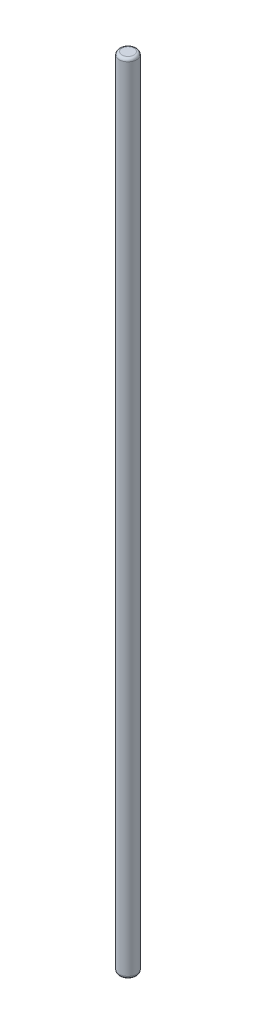
SolidWorks part; units mm, degrees
ref_plane "Front Plane" through (0, 0, 0) normal (0, 0, 1) x (1, 0, 0)
ref_plane "Top Plane" through (0, 0, 0) normal (0, 1, 0) x (1, 0, 0)
ref_plane "Right Plane" through (0, 0, 0) normal (1, 0, 0) x (0, 0, -1)
sketch "Sketch1" plane through (0, 0, 0) normal (0, 1, 0) x (1, 0, 0)
  circle A0 centre (0, 0) radius 0.95
  dimension "D1" = 1.9
extrude "Boss-Extrude1" add sketch "Sketch1" along normal blind 87
fillet "Fillet1" radius 0.3 2 edges at (0, 0, 0.95) (0, 87, 0.95)
